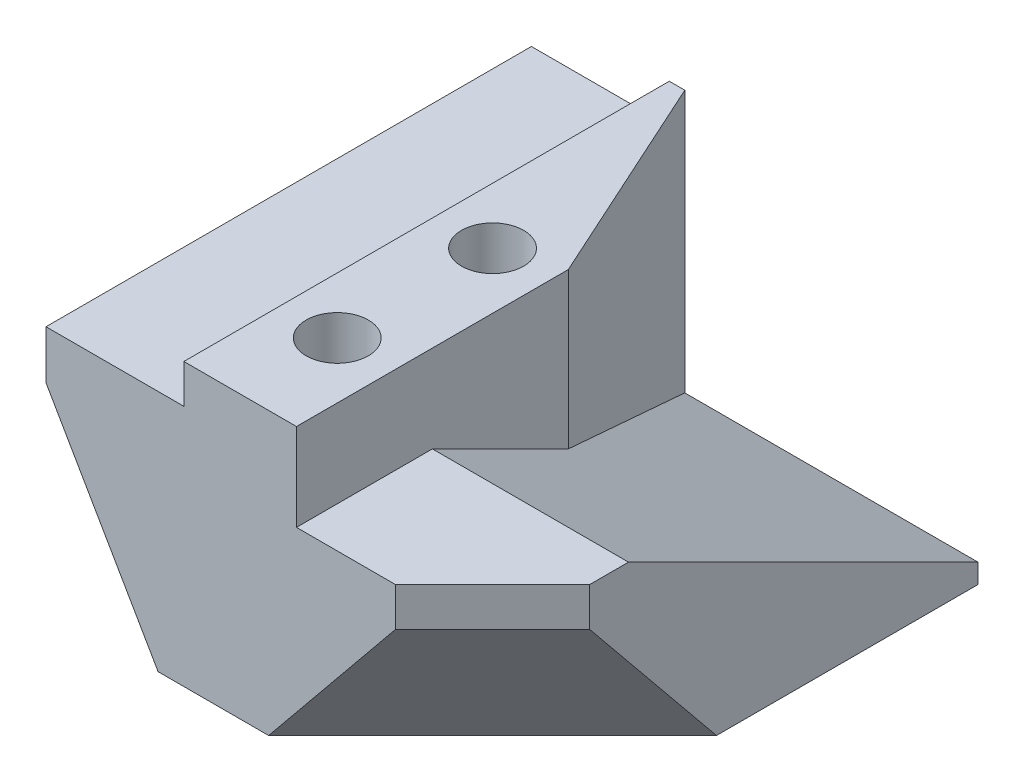
SolidWorks part; units mm, degrees
ref_plane "前视基准面" through (0, 0, 0) normal (0, 0, 1) x (1, 0, 0)
ref_plane "上视基准面" through (0, 0, 0) normal (0, 1, 0) x (1, 0, 0)
ref_plane "右视基准面" through (0, 0, 0) normal (1, 0, 0) x (0, 0, -1)
other "Configuration Table"
sketch "草图1" plane through (0, 0, 0) normal (0, 1, 0) x (1, 0, 0)
  line L1 (0, 0) -> (20, 0)
  line L2 (0, 0) -> (0, 20)
  line L3 (0, 20) -> (20, 20)
  line L4 (20, 0) -> (20, 20)
  dimension "D1" = 20
  dimension "D2" = 20
extrude "凸台-拉伸1" add sketch "草图1" along normal blind 4
sketch "草图2" plane through (0, 4, 0) normal (0, 1, 0) x (1, 0, 0)
  line L0 (0, 0) -> (20, 0) construction
  line L1 (0, 20) -> (12.9, 20)
  line L2 (0, 20) -> (0, 0)
  line L3 (0, 0) -> (12.9, 0)
  line L4 (12.9, 20) -> (12.9, 0)
  line L5 (20, 0) -> (20, 20) construction
  dimension "D1" = 7.1
extrude "凸台-拉伸2" add sketch "草图2" along normal blind 4.5
sketch "草图3" plane through (0, 0, 0) normal (0, -1, 0) x (-1, 0, 0)
  line L0 (0, 20) -> (0, 0) construction
  line L2 (0, 0) -> (-20, 0) construction
  circle A0 centre (-10, 5) radius 1.6
  circle A1 centre (-10, 13) radius 1.6
  dimension "D1" = 3.2
  dimension "D3" = 5
  dimension "D2" = 10
  dimension "D4" = 2
extrude "切除-拉伸1" cut sketch "草图3" against normal through all
sketch "草图4" plane through (0, 8.5, 0) normal (0, 1, 0) x (1, 0, 0)
  line L0 (12.9, 20) -> (0, 20) construction
  line L1 (7.1, 20) -> (12.9, 20)
  line L2 (7.1, 20) -> (7.1, 0)
  line L3 (7.1, 0) -> (12.9, 0)
  line L4 (12.9, 20) -> (12.9, 0)
  line L5 (0, 20) -> (0, 0) construction
  circle A0 centre (10, 13) radius 1.6
  circle A1 centre (10, 5) radius 1.6
  point P6 (10, 20)
  dimension "D1" = 5.8
  dimension "D2" = 10
extrude "凸台-拉伸3" add sketch "草图4" along normal blind 2
sketch "草图5" plane through (0, 0, 0) normal (0, -1, 0) x (-1, 0, 0)
  circle A0 centre (-10, 5) radius 3
  circle A1 centre (-10, 13) radius 3
  dimension "D1" = 6
  dimension "D2" = 6
extrude "切除-拉伸3" cut sketch "草图5" against normal blind 2.4
sketch "草图6" plane through (20, 0, 0) normal (1, 0, 0) x (0, 0, -1)
  line L1 (20, 0) -> (0, 0)
  line L2 (20, 0) -> (20, 4)
  line L3 (20, 4) -> (0, 4)
  line L4 (0, 0) -> (0, 4)
extrude "凸台-拉伸4" add sketch "草图6" along normal blind 3
sketch "草图7" plane through (0, 0, 0) normal (0, -1, 0) x (-1, 0, 0)
  line L1 (-23, 20) -> (0, 20)
  line L2 (-23, 20) -> (-23, 0)
  line L3 (-23, 0) -> (0, 0)
  line L4 (0, 20) -> (0, 0)
  circle A0 centre (-10, 13) radius 3
  circle A1 centre (-10, 5) radius 3
extrude "凸台-拉伸5" add sketch "草图7" along normal blind 4
sketch "草图9" plane through (0, 4, 0) normal (0, 1, 0) x (1, 0, 0)
  line L1 (23, 20) -> (12.9, 20)
  line L2 (23, 20) -> (23, 0)
  line L3 (23, 0) -> (12.9, 0)
  line L4 (12.9, 20) -> (12.9, 0)
extrude "凸台-拉伸6" add sketch "草图9" along normal blind 2
sketch "草图11" plane through (0, 0, -20) normal (0, 0, -1) x (-1, 0, 0)
  line L20 (-23, 6) -> (-23, -4)
  line L21 (-23, -4) -> (0, -4)
  line L22 (0, -4) -> (0, 8.5)
  line L23 (0, 8.5) -> (-7.1, 8.5)
  line L24 (-7.1, 8.5) -> (-7.1, 10.5)
  line L25 (-7.1, 10.5) -> (-12.9, 10.5)
  line L26 (-12.9, 10.5) -> (-12.9, 6)
  line L29 (-12.9, 6) -> (-23, 6)
  line L30 (-23, 6) -> (-23, -4)
  line L31 (-23, -4) -> (0, -4)
  line L32 (0, -4) -> (0, 8.5)
  line L33 (0, 8.5) -> (-7.1, 8.5)
  line L34 (-7.1, 8.5) -> (-7.1, 10.5)
  line L35 (-7.1, 10.5) -> (-12.9, 10.5)
  line L36 (-12.9, 10.5) -> (-12.9, 6)
  line L39 (-12.9, 6) -> (-23, 6)
  dimension "D1" = 0
extrude "凸台-拉伸7" add sketch "草图11" along normal blind 5
chamfer "倒角7" distance 10 angle 30 1 edges at (0, -4, -12.5) first distance on face at (0, 2.25, -12.5)
chamfer "倒角8" distance 5 angle 45 1 edges at (23, 1, 0)
chamfer "倒角9" distance 8 angle 30 1 edges at (20.5, -4, -2.5) first distance on face at (20.5, 1, -2.5)
sketch "草图15" plane through (23, 0, 0) normal (1, 0, 0) x (0, 0, -1)
  line L0 (25, -3) -> (25, 6)
  line L1 (25, 6) -> (25, -4) construction
  line L2 (25, 6) -> (7, 6)
  line L3 (25, 6) -> (0, 6) construction
  line L4 (7, 6) -> (25, -3)
  dimension "D1" = 9
  dimension "D2" = 18
extrude "切除-拉伸9" cut sketch "草图15" against normal up to surface (10.1 mm away) up to face at (12.9, 8.25, -12.5)
sketch "草图16" plane through (0, 10.5, 0) normal (0, 1, 0) x (1, 0, 0)
  line L0 (7.9, 25) -> (12.9, 25)
  line L1 (7.1, 25) -> (12.9, 25) construction
  line L2 (12.9, 7) -> (12.9, 25) construction
  line L3 (12.9, 0) -> (12.9, 25) construction
  line L4 (12.9, 25) -> (12.9, 14)
  line L5 (12.9, 14) -> (7.9, 25)
  dimension "D1" = 5
  dimension "D2" = 11
extrude "切除-拉伸10" cut sketch "草图16" against normal up to surface (8 mm away) up to face at (17.95, 1.5, -16)
chamfer "倒角10" distance 1.5 angle 45 2 edges at (10, 2.4, -14.6) (10, 2.4, -6.6)
